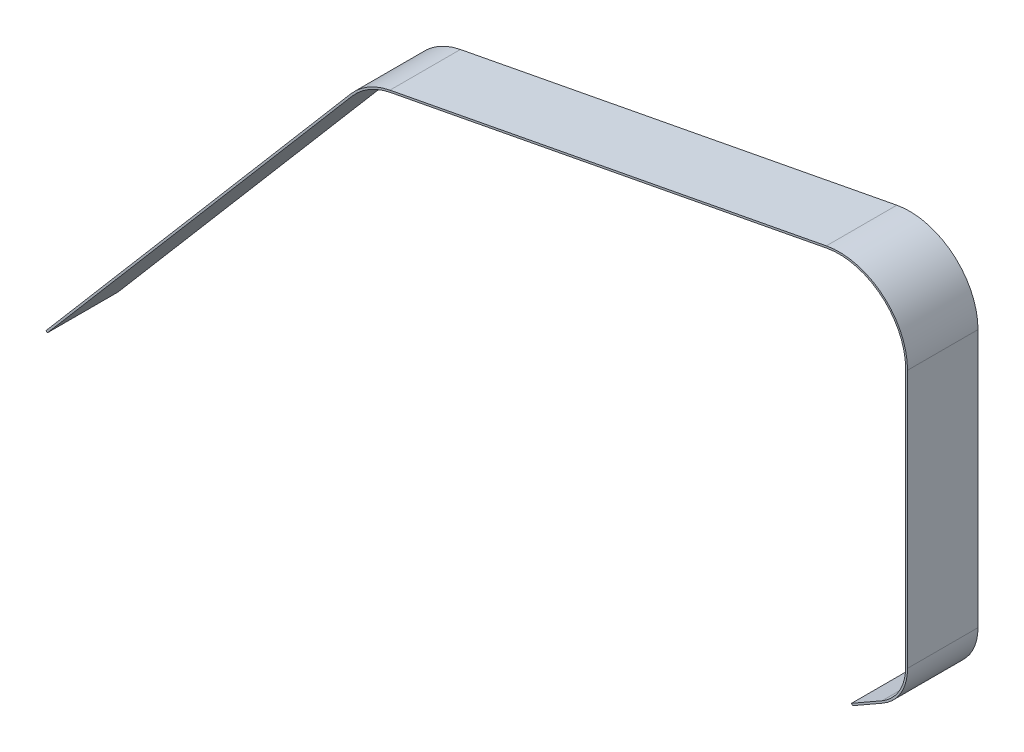
SolidWorks part; units mm, degrees
ref_plane "Front Plane" through (0, 0, 0) normal (0, 0, 1) x (1, 0, 0)
ref_plane "Top Plane" through (0, 0, 0) normal (0, 1, 0) x (1, 0, 0)
ref_plane "Right Plane" through (0, 0, 0) normal (1, 0, 0) x (0, 0, -1)
sketch "Sketch1" plane through (0, 0, 0) normal (0, 0, 1) x (1, 0, 0)
  line L0 (-6.9353, 36.3108) -> (229.0527, 81.3841)
  line L1 (0, 0) -> (17.6031, 3.3622) construction
  line L2 (229.0527, 81.3841) -> (236.3186, 43.342) construction
  line L6 (-6.9353, 36.3108) -> (0, 0) construction
  line L7 (-6.7447, 35.3129) -> (229.2432, 80.3863)
  line L8 (271.9391, 45.1566) -> (271.9391, -94.5434)
  line L9 (271.9391, -94.5434) -> (246.5391, -94.5434) construction
  line L10 (259.1738, -116.5781) -> (242.6638, -126.0449)
  line L11 (242.6638, -126.0449) -> (243.1692, -126.9263)
  line L12 (272.9551, 45.0733) -> (272.9551, -94.5125)
  line L13 (259.1738, -116.5781) -> (260.3002, -118.5425) construction
  line L14 (243.1692, -126.9263) -> (259.6792, -117.4594)
  line L15 (-28.1294, 23.9856) -> (-26.1434, 22.2922) construction
  line L19 (-28.1294, 23.9856) -> (-192.9335, -169.2904)
  line L20 (-192.9335, -169.2904) -> (-192.1604, -169.9496)
  line L21 (-192.1604, -169.9496) -> (-27.3564, 23.3264)
  arc A0 (-28.1294, 23.9856) -> (-6.9353, 36.3108) centre (0, 0) cw
  arc A1 (229.0527, 81.3841) -> (272.9551, 45.0733) centre (235.988, 45.0733) cw
  arc A2 (-27.3564, 23.3264) -> (-6.7447, 35.3129) centre (0, 0) cw
  arc A3 (271.9391, 45.1566) -> (229.2432, 80.3863) centre (235.988, 45.0733) ccw
  arc A4 (271.9391, -94.5434) -> (259.1738, -116.5781) centre (246.5391, -94.5434) cw
  arc A5 (272.9551, -94.5125) -> (259.6792, -117.4594) centre (246.5391, -94.5434) cw
  dimension "D5" = 36.9672
  dimension "D3" = 139.7
  dimension "D4" = 25.4
  dimension "D8" = 26.416
  dimension "D1" = 254
  dimension "D2" = 1.016
  dimension "D6" = 16.51
  dimension "D7" = 1.016
extrude "Boss-Extrude1" add sketch "Sketch1" along normal blind 38.1 contours A3 A1 L0 A0 A2 L7 region at (111.158, 58.3272, 0)
